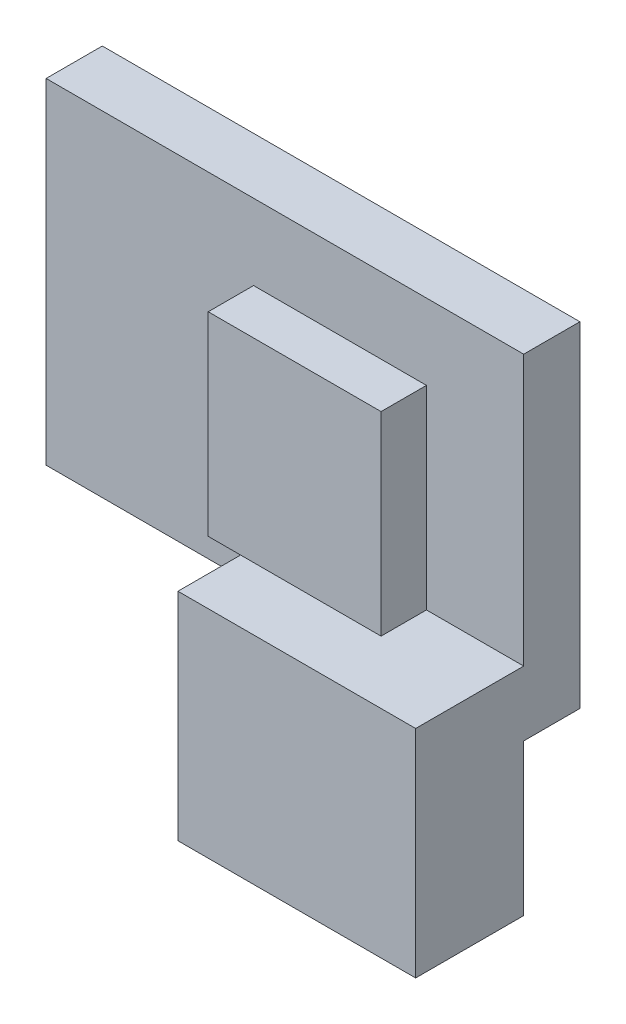
SolidWorks part; units mm, degrees
ref_plane "Plano frontal" through (0, 0, 0) normal (0, 0, 1) x (1, 0, 0)
ref_plane "Plano superior" through (0, 0, 0) normal (0, 1, 0) x (1, 0, 0)
ref_plane "Plano direito" through (0, 0, 0) normal (1, 0, 0) x (0, 0, -1)
sketch "PlacaEsboco" plane through (0, 0, 0) normal (0, 0, 1) x (1, 0, 0)
  line L1 (-11.05, -7.75) -> (11.05, -7.75)
  line L2 (-11.05, -7.75) -> (-11.05, 7.75)
  line L3 (-11.05, 7.75) -> (11.05, 7.75)
  line L4 (11.05, -7.75) -> (11.05, 7.75)
  line L5 (-11.05, -7.75) -> (11.05, 7.75) construction
  line L6 (-11.05, 7.75) -> (11.05, -7.75) construction
  point P0 (0, 0)
  dimension "D1" = 15.5
  dimension "D2" = 22.1
extrude "Placa" add sketch "PlacaEsboco" along normal mid plane 2.6
sketch "ConectorEsboco" plane through (0, 0, 1.3) normal (0, 0, 1) x (1, 0, 0)
  line L0 (11.05, -7.75) -> (11.05, 7.75) construction
  line L1 (11.05, -4.75) -> (0.05, -4.75)
  line L2 (11.05, -4.75) -> (11.05, -14.75)
  line L3 (11.05, -14.75) -> (0.05, -14.75)
  line L4 (0.05, -4.75) -> (0.05, -14.75)
  dimension "D1" = 11
  dimension "D2" = 10
  dimension "D3" = 3
extrude "Conector" add sketch "ConectorEsboco" along normal blind 5
sketch "ResistoresEsboco" plane through (0, 0, 1.3) normal (0, 0, 1) x (1, 0, 0)
  line L0 (11.05, -4.75) -> (0.05, -4.75) construction
  line L1 (6.55, 4.25) -> (-1.45, 4.25)
  line L2 (6.55, 4.25) -> (6.55, -4.75)
  line L3 (6.55, -4.75) -> (-1.45, -4.75)
  line L4 (-1.45, 4.25) -> (-1.45, -4.75)
  dimension "D1" = 12.5
  dimension "D2" = 4.5
  dimension "D3" = 3.5
extrude "Resistores" add sketch "ResistoresEsboco" along normal blind 2.1
sketch "PosLedLDR" plane through (0, 0, 1.3) normal (0, 0, 1) x (1, 0, 0)
  line L0 (11.05, 7.75) -> (-11.05, 7.75) construction
  line L1 (-11.05, 7.75) -> (-11.05, -7.75) construction
  circle A0 centre (-7.05, 5.75) radius 0.25
  circle A1 centre (-7.05, 4.25) radius 0.25
  circle A2 centre (-7.05, -4.75) radius 0.25
  circle A3 centre (-7.05, -6.25) radius 0.25
  point P0 (-7.05, 5.75)
  point P1 (-7.05, 4.25)
  point P2 (-7.05, -4.75)
  point P3 (-7.05, -6.25)
  dimension "D6" = 0.5
  dimension "D7" = 0.5
  dimension "D8" = 0.5
  dimension "D9" = 0.5
  dimension "D1" = 2
  dimension "D2" = 4
  dimension "D3" = 1.5
  dimension "D4" = 1.5
  dimension "D5" = 9
